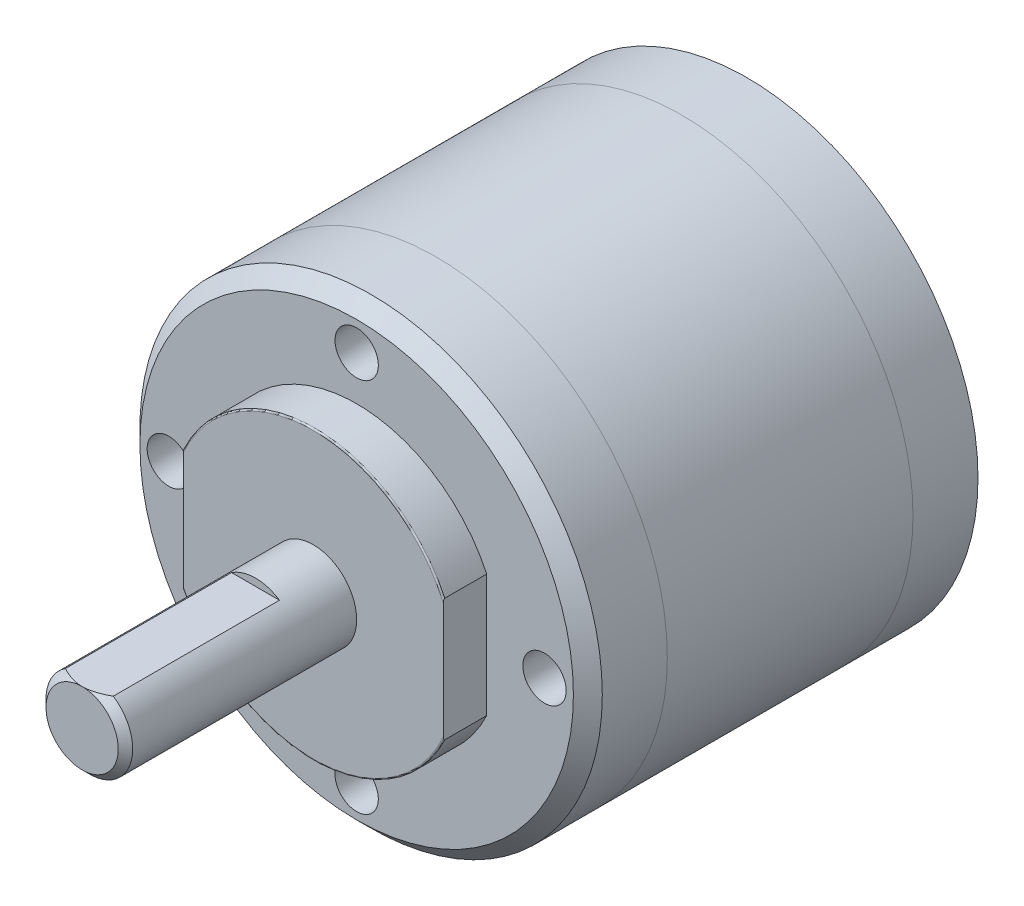
SolidWorks part; units mm, degrees
ref_plane "正面" through (0, 0, 0) normal (0, 0, 1) x (1, 0, 0)
ref_plane "平面" through (0, 0, 0) normal (0, 1, 0) x (1, 0, 0)
ref_plane "右側面" through (0, 0, 0) normal (1, 0, 0) x (0, 0, -1)
sketch "ｽｹｯﾁ1" plane through (0, 0, 0) normal (0, 0, 1) x (1, 0, 0)
  circle A0 centre (0, 0) radius 16
  dimension "D1" = 32
extrude "ﾎﾞｽ - 押し出し1" add sketch "ｽｹｯﾁ1" along normal blind 4.5
sketch "ｽｹｯﾁ2" plane through (0, 0, 4.5) normal (0, 0, 1) x (1, 0, 0)
  circle A0 centre (0, 0) radius 16
  dimension "D1" = 32
extrude "ﾎﾞｽ - 押し出し2" add sketch "ｽｹｯﾁ2" along normal blind 17 separate body
sketch "ｽｹｯﾁ3" plane through (0, 0, 21.5) normal (0, 0, 1) x (1, 0, 0)
  circle A0 centre (0, 0) radius 16
  dimension "D1" = 32
extrude "ﾎﾞｽ - 押し出し3" add sketch "ｽｹｯﾁ3" along normal blind 5.5 separate body
chamfer "面取り1" distance 1 angle 45 1 edges at (16, 0, 27)
sketch "ｽｹｯﾁ4" plane through (0, 0, 27) normal (0, 0, 1) x (1, 0, 0)
  line L0 (-9, 4.2429) -> (-9, -4.2429)
  line L1 (9, -4.2429) -> (9, 4.2429)
  arc A0 (-9, -4.2429) -> (9, -4.2429) centre (0, 0) ccw
  arc A1 (9, 4.2429) -> (-9, 4.2429) centre (0, 0) ccw
  dimension "D1" = 19.9
  dimension "D2" = 18
extrude "ﾎﾞｽ - 押し出し4" add sketch "ｽｹｯﾁ4" along normal blind 3
fillet "ﾌｨﾚｯﾄ1" radius 0.1 2 edges at (0, 9.95, 30) (0, -9.95, 30)
sketch "ｽｹｯﾁ5" plane through (0, 0, 30) normal (0, 0, 1) x (1, 0, 0)
  circle A0 centre (0, 0) radius 3
  dimension "D1" = 6
extrude "ﾎﾞｽ - 押し出し5" add sketch "ｽｹｯﾁ5" along normal blind 16
sketch "ｽｹｯﾁ6" plane through (0, 0, 46) normal (0, 0, 1) x (1, 0, 0)
  line L0 (-1.6583, 2.5) -> (1.6583, 2.5)
  arc A0 (1.6583, 2.5) -> (-1.6583, 2.5) centre (0, 0) ccw
  dimension "D1" = 6
  dimension "D2" = 2.5
extrude "ｶｯﾄ - 押し出し1" cut sketch "ｽｹｯﾁ6" against normal blind 12
chamfer "面取り2" distance 0.5 angle 45 1 edges at (0, -3, 46)
sketch "ｽｹｯﾁ7" plane through (0, 0, 27) normal (0, 0, 1) x (1, 0, 0)
  line L0 (-16, 0) -> (16, 0) construction
  line L1 (0, 16) -> (0, -16) construction
  circle A0 centre (0, 0) radius 16 construction
  circle A1 centre (0, 13) radius 1.5
  circle A2 centre (13, 0) radius 1.5
  circle A3 centre (0, -13) radius 1.5
  circle A4 centre (-13, 0) radius 1.5
  dimension "D1" = 3
  dimension "D2" = 26
  dimension "D3" = 26
  dimension "D4" = 13
  dimension "D5" = 13
extrude "ｶｯﾄ - 押し出し2" cut sketch "ｽｹｯﾁ7" against normal blind 4
sketch "ｽｹｯﾁ8" plane through (0, 0, 0) normal (0, 0, -1) x (-1, 0, 0)
  line L0 (-16, 0) -> (16, 0) construction
  line L1 (0, 8) -> (0, -8) construction
  circle A0 centre (0, 0) radius 16 construction
  circle A1 centre (0, 0) radius 6
  circle A2 centre (12.5, 0) radius 1.6
  circle A3 centre (-12.5, 0) radius 1.6
  circle A4 centre (0, 8) radius 1.6
  circle A5 centre (0, -8) radius 1.6
  dimension "D1" = 25
  dimension "D2" = 3.2
  dimension "D4" = 12
  dimension "D3" = 12.5
  dimension "D5" = 16
extrude "ｶｯﾄ - 押し出し3" cut sketch "ｽｹｯﾁ8" against normal blind 10
chamfer "面取り3" distance 0.3 angle 45 1 edges at (-6, 0, 0)
sketch "ｽｹｯﾁ9" plane through (0, 0, 30) normal (0, 0, 1) x (1, 0, 0)
  circle A0 centre (0, 0) radius 7
  dimension "D1" = 14
extrude "ﾎﾞｽ - 押し出し6" [suppressed] add sketch "ｽｹｯﾁ9" along normal blind 1
